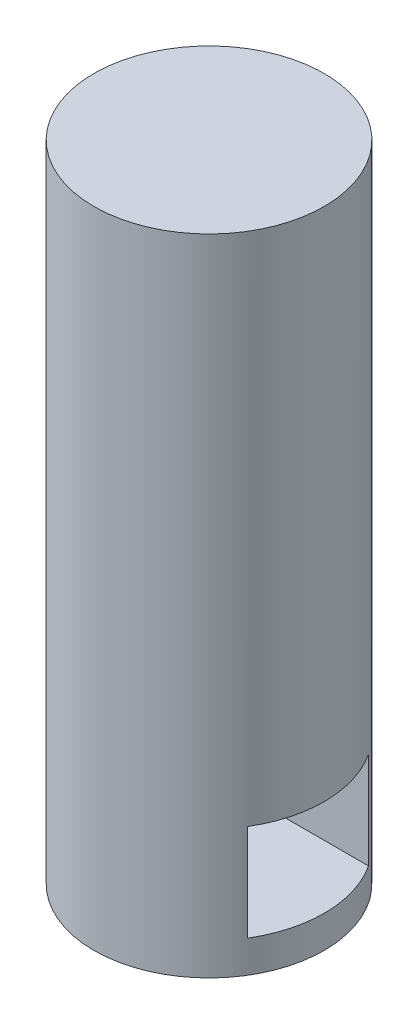
SolidWorks part; units mm, degrees
ref_plane "Front Plane" through (0, 0, 0) normal (0, 0, 1) x (1, 0, 0)
ref_plane "Top Plane" through (0, 0, 0) normal (0, 1, 0) x (1, 0, 0)
ref_plane "Right Plane" through (0, 0, 0) normal (1, 0, 0) x (0, 0, -1)
sketch "Sketch1" plane through (0, 0, 0) normal (0, 1, 0) x (1, 0, 0)
  circle A0 centre (0, 0) radius 7.15
extrude "Boss-Extrude1" add sketch "Sketch1" along normal blind 40
sketch "Sketch2" plane through (0, 0, 0) normal (0, -1, 0) x (1, 0, 0)
  circle A0 centre (0, 0) radius 1
extrude "Cut-Extrude1" cut sketch "Sketch2" against normal blind 4
ref_plane "Plane1" through (0, 2, 0) normal (0, 1, 0) x (1, 0, 0)
sketch "Sketch3" plane through (0, 2, 0) normal (0, 1, 0) x (1, 0, 0)
  line L1 (-7.5477, 3.9185) -> (7.3941, 3.9185)
  line L2 (-7.5477, 3.9185) -> (-7.5477, -3.7241)
  line L3 (-7.5477, -3.7241) -> (7.3941, -3.7241)
  line L4 (7.3941, 3.9185) -> (7.3941, -3.7241)
extrude "Cut-Extrude2" cut sketch "Sketch3" along normal blind 6
sketch "Sketch4" plane through (0, -2, 0) normal (0, -1, 0) x (1, 0, 0)
  circle A0 centre (0, 0) radius 1 construction
  circle A1 centre (0, 0) radius 1
